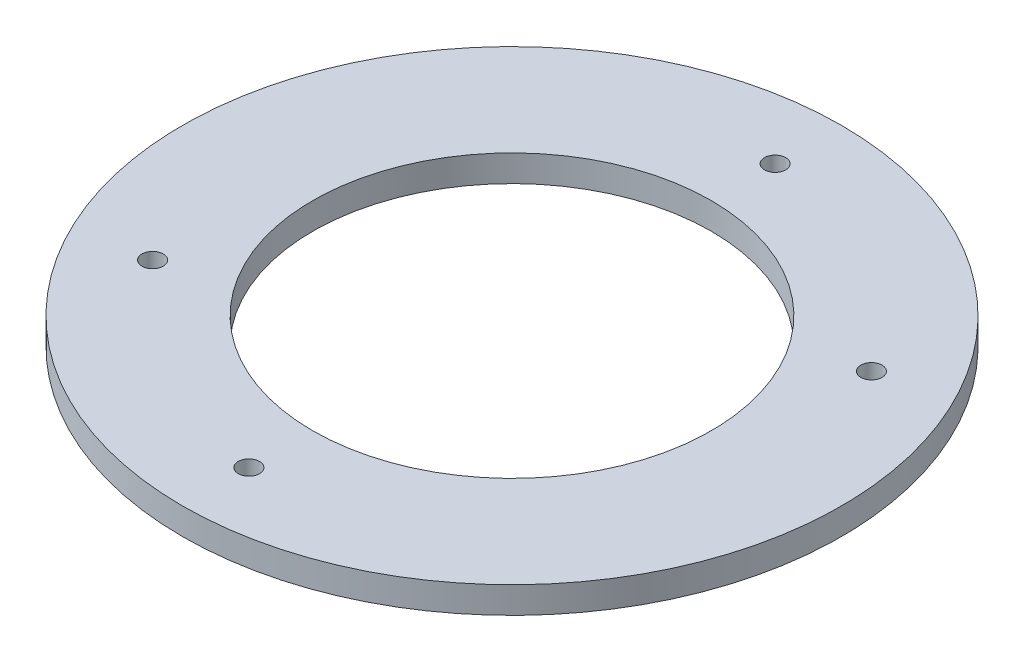
SolidWorks part; units mm, degrees
ref_plane "Front Plane" through (0, 0, 0) normal (0, 0, 1) x (1, 0, 0)
ref_plane "Top Plane" through (0, 0, 0) normal (0, 1, 0) x (1, 0, 0)
ref_plane "Right Plane" through (0, 0, 0) normal (1, 0, 0) x (0, 0, -1)
sketch "Sketch1" plane through (0, 0, 0) normal (0, 1, 0) x (1, 0, 0)
  circle A0 centre (0, 0) radius 62
  dimension "D1" = 124
extrude "Boss-Extrude1" add sketch "Sketch1" along normal blind 5
sketch "Sketch2" plane through (0, 5, 0) normal (0, 1, 0) x (1, 0, 0)
  circle A0 centre (0, 49.5) radius 2
  dimension "D2" = 4
  dimension "D1" = 49.5
extrude "Cut-Extrude1" cut sketch "Sketch2" against normal blind 5 contours A0
pattern_circular "CirPattern1" count 2 every 120 about axis through (0, 5, 0) along (0, 1, 0) of "Cut-Extrude1"
sketch "Sketch4" plane through (0, 5, 0) normal (0, 1, 0) x (1, 0, 0)
  line L0 (0, 49.5) -> (-42.8683, -24.75) construction
  line L1 (0, 0) -> (-23.6703, -40.9981) construction
ref_plane "Plane1" through (0, 0, 0) normal (-0.866, 0, -0.5) x (-0.5, 0, 0.866)
mirror "Mirror1" about plane through (0, 0, 0) normal (-0.866, 0, -0.5) of "Cut-Extrude1", "CirPattern1"
sketch "Sketch5" plane through (0, 0, 0) normal (0, -1, 0) x (1, 0, 0)
  circle A0 centre (0, 0) radius 37.5
  dimension "D1" = 75
extrude "Cut-Extrude2" cut sketch "Sketch5" against normal blind 10
